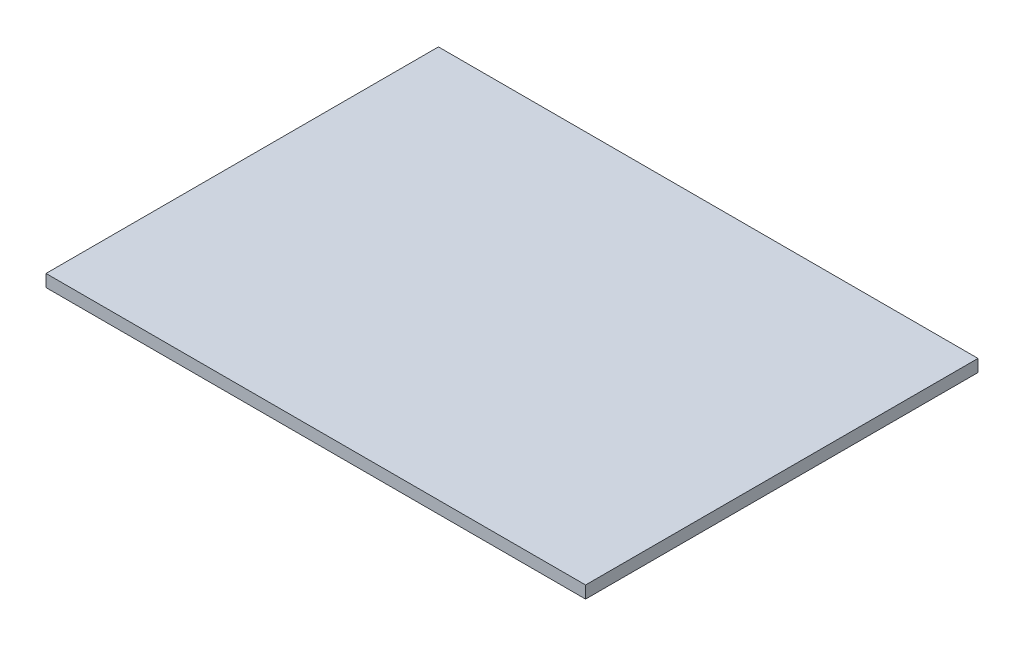
SolidWorks part; units mm, degrees
ref_plane "Front Plane" through (0, 0, 0) normal (0, 0, 1) x (1, 0, 0)
ref_plane "Top Plane" through (0, 0, 0) normal (0, 1, 0) x (1, 0, 0)
ref_plane "Right Plane" through (0, 0, 0) normal (1, 0, 0) x (0, 0, -1)
sketch "Sketch1" plane through (0, 0, 0) normal (0, 1, 0) x (1, 0, 0)
  line L1 (-139.7, -101.6) -> (139.7, -101.6)
  line L2 (-139.7, -101.6) -> (-139.7, 101.6)
  line L3 (-139.7, 101.6) -> (139.7, 101.6)
  line L4 (139.7, -101.6) -> (139.7, 101.6)
  line L5 (-139.7, -101.6) -> (139.7, 101.6) construction
  line L6 (-139.7, 101.6) -> (139.7, -101.6) construction
  point P0 (0, 0)
  dimension "D1" = 203.2
  dimension "D2" = 279.4
extrude "Boss-Extrude1" add sketch "Sketch1" along normal blind 6.35
sketch "Sketch2" plane through (0, 0, 0) normal (0, 1, 0) x (1, 0, 0)
  line L0 (-193.2668, 0) -> (192.9727, 0) construction
